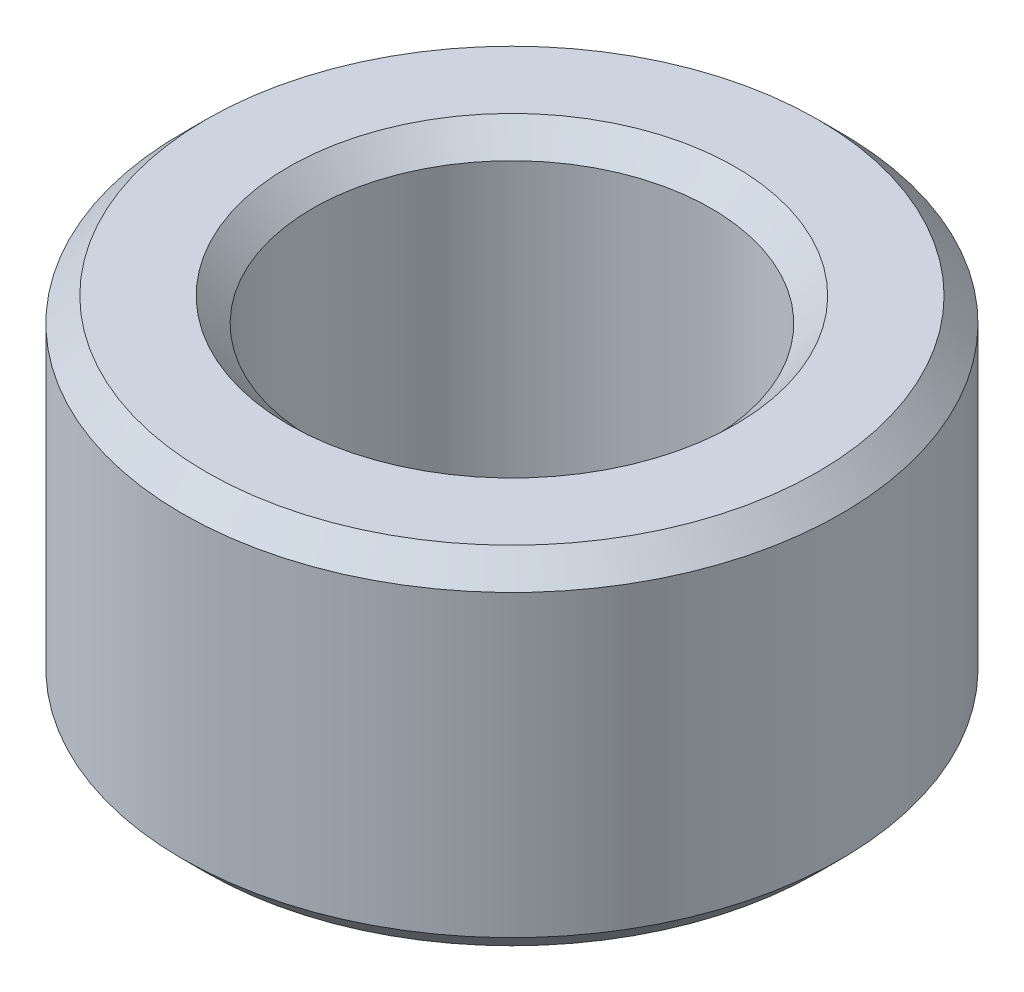
SolidWorks part; units mm, degrees
ref_plane "Front Plane" through (0, 0, 0) normal (0, 0, 1) x (1, 0, 0)
ref_plane "Top Plane" through (0, 0, 0) normal (0, 1, 0) x (1, 0, 0)
ref_plane "Right Plane" through (0, 0, 0) normal (1, 0, 0) x (0, 0, -1)
sketch "Sketch1" plane through (0, 0, 0) normal (0, 1, 0) x (1, 0, 0)
  circle A0 centre (0, 0) radius 50
  dimension "SLEEVE_OD" = 100
extrude "Boss-Extrude1" add sketch "Sketch1" along normal blind 52.6282
sketch "Sketch2" plane through (0, 0, 0) normal (0, 1, 0) x (1, 0, 0)
  circle A0 centre (0, 0) radius 30.2384
  dimension "BORE_D" = 60.4767
extrude "Cut-Extrude1" cut sketch "Sketch2" along normal through all
chamfer "Chamfer1" distance 3.6383 angle 45 4 edges at (0, 52.6282, 30.2384) (0, 0, 30.2384) (0, 0, 50) (0, 52.6282, 50)
